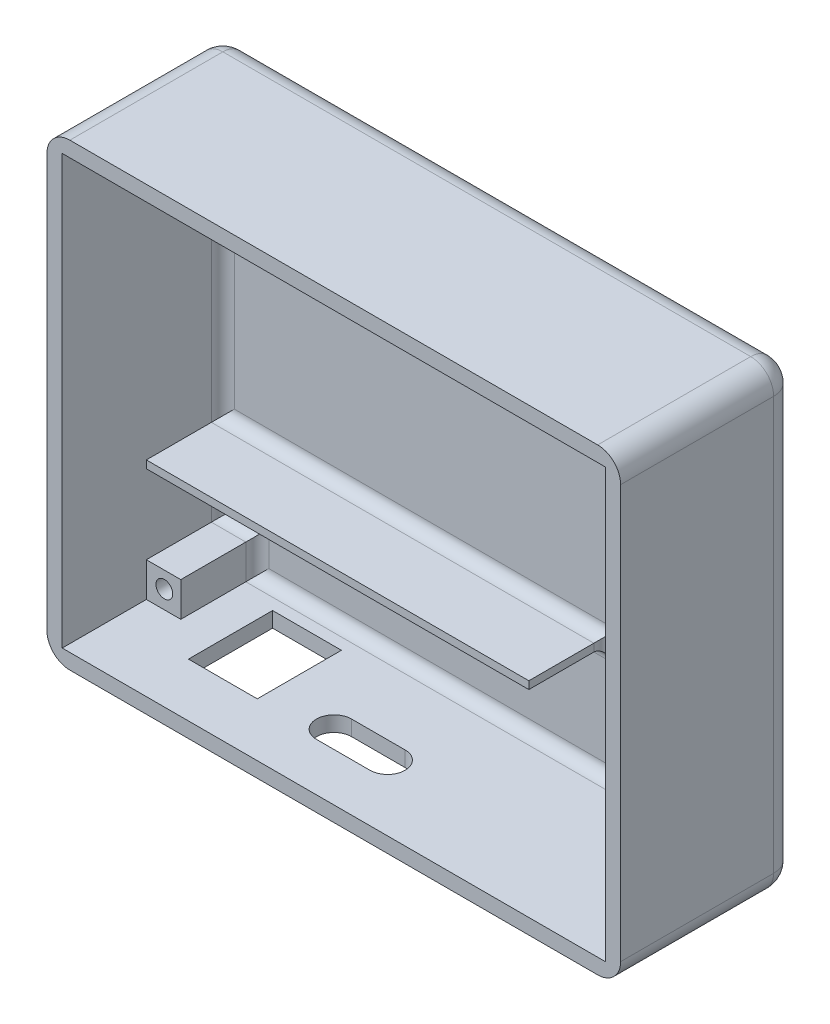
SolidWorks part; units mm, degrees
ref_plane "Front Plane" through (0, 0, 0) normal (0, 0, 1) x (1, 0, 0)
ref_plane "Top Plane" through (0, 0, 0) normal (0, 1, 0) x (1, 0, 0)
ref_plane "Right Plane" through (0, 0, 0) normal (1, 0, 0) x (0, 0, -1)
sketch "Sketch2" plane through (0, 0, 0) normal (0, 0, 1) x (1, 0, 0)
  line L1 (0, 0) -> (75, 0)
  line L2 (0, 0) -> (0, 60)
  line L3 (0, 60) -> (75, 60)
  line L4 (75, 0) -> (75, 60)
  dimension "D1" = 75
  dimension "D2" = 60
extrude "Body creation" add sketch "Sketch2" along normal blind 23
shell "Thikness of walls" thickness 2 removed face at (37.5, 30, 23)
ref_plane "Plane1" through (0, 30, 0) normal (0, -1, 0) x (-1, 0, 0)
sketch "Sketch6" plane through (0, 0, 2) normal (0, 0, 1) x (1, 0, 0)
  line L1 (2, 58) -> (6.5, 58)
  line L2 (2, 58) -> (2, 53.5)
  line L3 (2, 53.5) -> (6.5, 53.5)
  line L4 (6.5, 58) -> (6.5, 53.5)
  line L5 (73, 58) -> (68.5, 58)
  line L6 (73, 58) -> (73, 53.5)
  line L7 (73, 53.5) -> (68.5, 53.5)
  line L8 (68.5, 58) -> (68.5, 53.5)
  dimension "D1" = 4.5
extrude "Corner rect." add sketch "Sketch6" along normal blind 10
sketch "Sketch8" plane through (0, 0, 23) normal (0, 0, 1) x (1, 0, 0)
  line L0 (4.35, 55.65) -> (4.35, 53.5) construction
  line L1 (2, 53.5) -> (6.5, 53.5) construction
  line L2 (6.5, 55.65) -> (4.35, 55.65) construction
  line L3 (6.5, 53.5) -> (6.5, 58) construction
  line L4 (68.5, 55.65) -> (70.65, 55.65) construction
  line L7 (70.65, 55.65) -> (70.65, 53.5) construction
  line L9 (68.5, 58) -> (68.5, 53.5) construction
  line L10 (68.5, 53.5) -> (73, 53.5) construction
  circle A0 centre (4.35, 55.65) radius 1.1
  circle A1 centre (70.65, 55.65) radius 1.1
  dimension "D1" = 2.2
  dimension "D2" = 2.15
  dimension "D3" = 2.15
extrude "Screw hole" cut sketch "Sketch8" against normal up to surface (23 mm away) up to face at (37.5, 30, 0)
sketch "Sketch10" plane through (0, 0, 0) normal (0, 0, -1) x (-1, 0, 0)
  circle A0 centre (-70.65, 55.65) radius 1.85
  circle A1 centre (-4.35, 55.65) radius 1.85
  dimension "D1" = 3.7
extrude "Screw head" cut sketch "Sketch10" against normal blind 4
mirror "Mirror to other side" about plane through (0, 30, 0) normal (0, -1, 0) of "Screw head", "Corner rect.", "Screw hole"
sketch "Sketch5" plane through (0, 0, 0) normal (0, -1, 0) x (1, 0, 0)
  line L0 (0, 0) -> (75, 0) construction
  line L1 (20.5, 16) -> (11.5, 16)
  line L2 (20.5, 16) -> (20.5, 5)
  line L3 (20.5, 5) -> (11.5, 5)
  line L4 (11.5, 16) -> (11.5, 5)
  line L5 (0, 23) -> (0, 0) construction
  line L6 (28.95, 14.42) -> (35.95, 14.42) construction
  line L7 (16, 16) -> (16, 5) construction
  line L9 (28.95, 16.72) -> (35.95, 16.72)
  line L10 (28.95, 12.12) -> (35.95, 12.12)
  arc A0 (28.95, 16.72) -> (28.95, 12.12) centre (28.95, 14.42) ccw
  arc A1 (35.95, 12.12) -> (35.95, 16.72) centre (35.95, 14.42) ccw
  point P10 (32.45, 14.42)
  dimension "D6" = 2.3
  dimension "D1" = 11
  dimension "D2" = 9
  dimension "D3" = 16
  dimension "D4" = 16
  dimension "D5" = 7
  dimension "D7" = 11.95
  dimension "D8" = 0.72
extrude "Ports cut out" cut sketch "Sketch5" against normal up to surface (2 mm away) up to face at (37.5, 2, 12.25)
sketch "Sketch11" plane through (0, 0, 2) normal (0, 0, 1) x (1, 0, 0)
  line L0 (2, 53.5) -> (2, 6.5) construction
  line L1 (6.5, 53.5) -> (52, 53.5)
  line L3 (2, 17.8) -> (52, 17.8)
  line L5 (6.5, 54.5) -> (52, 54.5)
  line L6 (2, 16.8) -> (52, 16.8)
  line L7 (52, 17.8) -> (52, 16.8)
  line L8 (52, 54.5) -> (52, 53.5)
  line L9 (6.5, 54.5) -> (6.5, 53.5)
  line L10 (2, 17.8) -> (2, 16.8)
  line L11 (2, 58) -> (2, 2) construction
  line L12 (68.5, 58) -> (67.25, 58)
  line L13 (68.5, 58) -> (68.5, 35.5)
  line L14 (68.5, 35.5) -> (67.25, 35.5)
  line L15 (67.25, 58) -> (67.25, 35.5)
  line L16 (68.5, 58) -> (68.5, 53.5) construction
  line L18 (68.5, 58) -> (6.5, 58) construction
  dimension "D1" = 35.7
  dimension "D2" = 50
  dimension "D5" = 65.25
  dimension "D6" = 22.5
  dimension "D3" = 1
  dimension "D4" = 1
extrude "Battery Placement" add sketch "Sketch11" along normal blind 10
fillet "Fillet1" radius 1.5 20 edges at (2, 11.65, 2) (6.5, 56.25, 2) (29.25, 54.5, 2) (27, 16.8, 2) (2, 35.65, 2) (27, 53.5, 2) (52, 54, 2) (36.875, 58, 2) (70.75, 53.5, 2) (73, 30, 2) (70.75, 6.5, 2) (68.5, 4.25, 2) (37.5, 2, 2) (6.5, 4.25, 2) (4.25, 6.5, 2) (52, 17.3, 2) (27, 17.8, 2) (67.25, 46.75, 2) (67.875, 35.5, 2) (68.5, 44.5, 2)
fillet "Fillet2" radius 3 8 edges at (0, 60, 11.5) (75, 60, 11.5) (75, 0, 11.5) (0, 0, 11.5) (37.5, 60, 0) (75, 30, 0) (37.5, 0, 0) (0, 30, 0)
sketch "Sketch13" plane through (0, 0, 0) normal (0, 0, -1) x (-1, 0, 0)
  line L0 (-37.5, 50) -> (-37.5, 57) construction
  line L1 (-62.5, 50) -> (-12.5, 50)
  line L2 (-62.5, 50) -> (-62.5, 10)
  line L3 (-62.5, 10) -> (-12.5, 10)
  line L4 (-12.5, 50) -> (-12.5, 10)
  line L5 (-5.6149, 57) -> (-69.3851, 57) construction
  line L6 (-62.5, 30) -> (-72, 30) construction
  line L7 (-72, 54.3851) -> (-72, 5.6149) construction
  dimension "D1" = 50
  dimension "D2" = 40
extrude "Cut-Extrude1" cut sketch "Sketch13" against normal blind 1
